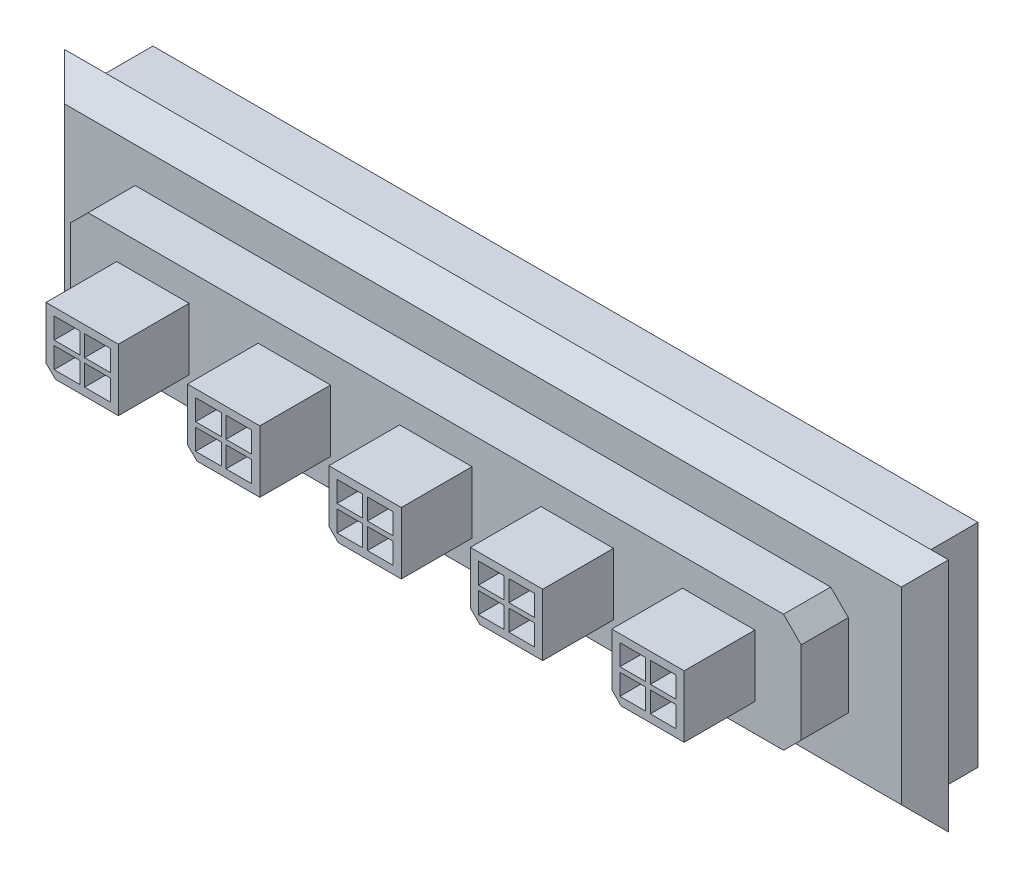
SolidWorks part; units mm, degrees
ref_plane "Front Plane" through (0, 0, 0) normal (0, 0, 1) x (1, 0, 0)
ref_plane "Top Plane" through (0, 0, 0) normal (0, 1, 0) x (1, 0, 0)
ref_plane "Right Plane" through (0, 0, 0) normal (1, 0, 0) x (0, 0, -1)
sketch "Sketch1" plane through (0, 0, 0) normal (0, 0, 1) x (1, 0, 0)
  line L1 (-37.5, 10) -> (37.5, 10)
  line L2 (-37.5, 10) -> (-37.5, -10)
  line L3 (-37.5, -10) -> (37.5, -10)
  line L4 (37.5, 10) -> (37.5, -10)
  line L5 (-37.5, 10) -> (37.5, -10) construction
  line L6 (-37.5, -10) -> (37.5, 10) construction
  point P0 (0, 0)
  dimension "D1" = 75
  dimension "D2" = 20
extrude "Boss-Extrude1" add sketch "Sketch1" along normal blind 2
sketch "Sketch2" plane through (0, 0, 2) normal (0, 0, 1) x (1, 0, 0)
  line L1 (-31, 5) -> (31, 5)
  line L2 (-31, 5) -> (-31, -5)
  line L3 (-31, -5) -> (31, -5)
  line L4 (31, 5) -> (31, -5)
  line L5 (-31, 5) -> (31, -5) construction
  line L6 (-31, -5) -> (31, 5) construction
  point P0 (0, 0)
  dimension "D1" = 62
  dimension "D2" = 10
extrude "Boss-Extrude2" add sketch "Sketch2" along normal blind 4
sketch "Sketch3" plane through (0, 0, 0) normal (0, 0, -1) x (-1, 0, 0)
  line L1 (-35, -9) -> (35, -9)
  line L2 (-35, -9) -> (-35, 9)
  line L3 (-35, 9) -> (35, 9)
  line L4 (35, -9) -> (35, 9)
  line L5 (-35, -9) -> (35, 9) construction
  line L6 (-35, 9) -> (35, -9) construction
  point P0 (0, 0)
  dimension "D1" = 70
  dimension "D2" = 18
extrude "Boss-Extrude3" add sketch "Sketch3" along normal blind 5
sketch "Sketch4" plane through (0, 0, 6) normal (0, 0, 1) x (1, 0, 0)
  line L1 (-3.0712, 2.6267) -> (3.0712, 2.6267)
  line L2 (-3.0712, 2.6267) -> (-3.0712, -2.6267)
  line L3 (-3.0712, -2.6267) -> (3.0712, -2.6267)
  line L4 (3.0712, 2.6267) -> (3.0712, -2.6267)
  line L5 (-3.0712, 2.6267) -> (3.0712, -2.6267) construction
  line L6 (-3.0712, -2.6267) -> (3.0712, 2.6267) construction
  point P0 (0, 0)
extrude "Boss-Extrude4" add sketch "Sketch4" along normal blind 6
sketch "Sketch5" plane through (0, 0, 12) normal (0, 0, 1) x (1, 0, 0)
  line L0 (0, 2.1717) -> (0, -2.1717)
  line L1 (-2.5812, 2.1717) -> (2.5812, 2.1717)
  line L2 (-2.5812, 2.1717) -> (-2.5812, -2.1717)
  line L3 (-2.5812, -2.1717) -> (2.5812, -2.1717)
  line L4 (2.5812, 2.1717) -> (2.5812, -2.1717)
  line L5 (-2.5812, 2.1717) -> (2.5812, -2.1717) construction
  line L6 (-2.5812, -2.1717) -> (2.5812, 2.1717) construction
  line L7 (-2.5812, 0) -> (2.5812, 0)
  line L8 (-0.2, 2.1717) -> (-0.2, -2.1717)
  line L9 (-2.5812, -0.2) -> (2.5812, -0.2)
  line L10 (0.2, 2.1717) -> (0.2, -2.1717)
  line L11 (-2.5812, 0.2) -> (2.5812, 0.2)
  line L12 (-2.3812, -1.9717) -> (2.3812, -1.9717)
  line L13 (2.3812, 1.9717) -> (2.3812, -1.9717)
  line L14 (-2.3812, 1.9717) -> (2.3812, 1.9717)
  line L15 (-2.3812, 1.9717) -> (-2.3812, -1.9717)
  line L16 (0.2, 2.1717) -> (0.2, 2.7306)
  line L17 (0.2, 2.7306) -> (-0.2, 2.7306)
  line L18 (-0.2, 2.7306) -> (-0.2, 2.1717)
  line L19 (2.5812, 0.2) -> (3.0712, 0.2)
  line L20 (3.0712, -2.6267) -> (3.0712, 2.6267) construction
  line L21 (3.0712, 0.2) -> (3.0712, -0.2)
  line L22 (3.0712, -2.6267) -> (3.0712, 2.6267) construction
  line L23 (3.0712, -0.2) -> (2.5812, -0.2)
  line L24 (0.2, -2.1717) -> (0.2, -2.6267)
  line L25 (-3.0712, -2.6267) -> (3.0712, -2.6267) construction
  line L26 (0.2, -2.6267) -> (-0.2, -2.6267)
  line L27 (-0.2, -2.6267) -> (-0.2, -2.1717)
  line L28 (-2.5812, 0.2) -> (-3.0712, 0.2)
  line L29 (-3.0712, 2.6267) -> (-3.0712, -2.6267) construction
  line L30 (-3.0712, 0.2) -> (-3.0712, -0.2)
  line L31 (-3.0712, 2.6267) -> (-3.0712, -2.6267) construction
  line L32 (-3.0712, -0.2) -> (-2.5812, -0.2)
  point P0 (0, 0)
  dimension "D1" = 0.2
  dimension "D2" = 0.2
  dimension "D3" = 0.2
sketch "Sketch6" plane through (0, 0, 12) normal (0, 0, 1) x (1, 0, 0)
  line L0 (0.2, 2.1717) -> (0.2, -2.1717) construction
  line L1 (2.3812, 1.9717) -> (0.2, 1.9717)
  line L2 (2.3812, 1.9717) -> (2.3812, 0.2)
  line L3 (2.3812, 0.2) -> (0.2, 0.2)
  line L4 (0.2, 1.9717) -> (0.2, 0.2)
  line L5 (-2.5812, 0.2) -> (2.5812, 0.2) construction
  line L6 (-0.2, 2.1717) -> (-0.2, -2.1717) construction
  line L7 (-2.3812, 1.9717) -> (-0.2, 1.9717)
  line L8 (-2.3812, 1.9717) -> (-2.3812, 0.2)
  line L9 (-2.3812, 0.2) -> (-0.2, 0.2)
  line L10 (-0.2, 1.9717) -> (-0.2, 0.2)
  line L11 (-2.5812, -0.2) -> (2.5812, -0.2) construction
  line L12 (-2.3812, -1.9717) -> (-0.2, -1.9717)
  line L13 (-2.3812, -1.9717) -> (-2.3812, -0.2)
  line L14 (-2.3812, -0.2) -> (-0.2, -0.2)
  line L15 (-0.2, -1.9717) -> (-0.2, -0.2)
  line L22 (2.3812, -1.9717) -> (0.2, -1.9717)
  line L23 (2.3812, -1.9717) -> (2.3812, -0.2)
  line L24 (2.3812, -0.2) -> (0.2, -0.2)
  line L25 (0.2, -1.9717) -> (0.2, -0.2)
extrude "Cut-Extrude1" cut sketch "Sketch6" against normal blind 6
pattern_linear "LPattern1" count 3 spacing 12 along (1, 0, 0) count 3 spacing 12 along (-1, 0, 0) of "Boss-Extrude4", "Cut-Extrude1"
chamfer "Chamfer1" distance 0.8 angle 45 5 edges at (20.9288, -2.6267, 9) (8.9288, -2.6267, 9) (-15.0712, -2.6267, 9) (-27.0712, -2.6267, 9) (-3.0712, -2.6267, 9)
chamfer "Chamfer2" distance 1.5 angle 45 4 edges at (-31, -5, 4) (-31, 5, 4) (31, -5, 4) (31, 5, 4)
chamfer "Chamfer4" distance 2 angle 45 4 edges at (0, 10, 2) (37.5, 0, 2) (0, -10, 2) (-37.5, 0, 2)
